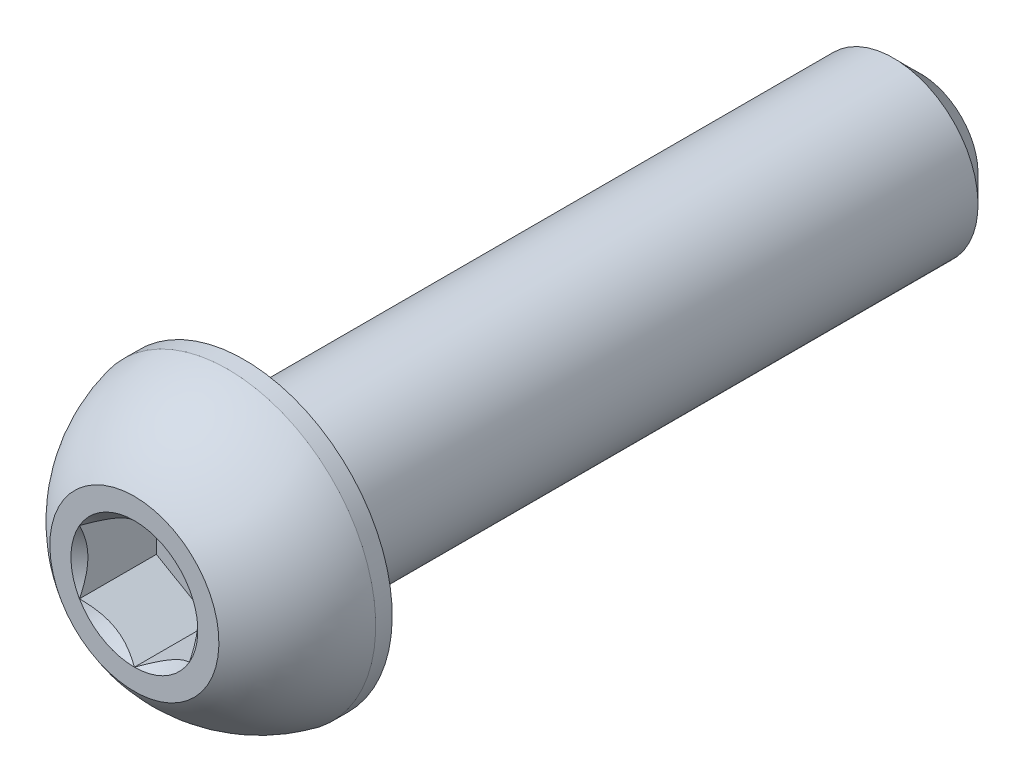
SolidWorks part; units mm, degrees
ref_plane "Front Plane" through (0, 0, 0) normal (0, 0, 1) x (1, 0, 0)
ref_plane "Top Plane" through (0, 0, 0) normal (0, 1, 0) x (1, 0, 0)
ref_plane "Right Plane" through (0, 0, 0) normal (1, 0, 0) x (0, 0, -1)
sketch "Sketch1" plane through (0, 0, 0) normal (1, 0, 0) x (0, 0, -1)
  line L0 (-4.65, 0) -> (4.65, 0) construction
  line L1 (-3.35, 1.75) -> (-3.35, -1.75) construction
  line L2 (4.65, 1) -> (4.65, -1) construction
  line L3 (4.625, 1.0433) -> (4.825, 0.6969) construction
  line L4 (4.825, 0.6969) -> (5.025, 1.0433) construction
  line L5 (5.025, 1.0433) -> (4.625, 1.0433) construction
  line L6 (4.65, 1) -> (5, 1) construction
  line L7 (4.825, 1.0433) -> (4.825, 1) construction
  line L8 (4.825, 1) -> (4.825, 0.7402) construction
  line L9 (4.825, 0.7402) -> (4.825, 0.6969) construction
  line L10 (4.8, 0.7402) -> (4.85, 0.7402)
  line L11 (4.6375, 1.0217) -> (5.0125, 1.0217)
  line L12 (4.85, 0.7402) -> (5.0125, 1.0217)
  line L13 (4.8, 0.7402) -> (4.6375, 1.0217)
  line L14 (-4.65, 0.65) -> (-4.65, -0.65) construction
  line L15 (4.65, 1) -> (-3.35, 1) construction
  point P3 (-3.35, 0)
  point P6 (-3.74, 0)
  point P21 (4.825, 1.0217)
  point P24 (-3.545, 1.75)
  point P25 (3.65, -1)
  point P26 (-4.65, 1)
  dimension "Head Height" = 1.3
  dimension "Length" = 8
  dimension "Head Dia" = 3.5
  dimension "Thread Dia" = 2
  dimension "Pitch" = 0.4
  dimension "D2" = 0.05
  dimension "Drive Size" = 1.3
  dimension "D1" = 0.91
  dimension "D3" = 0.195
  dimension "D4" = 1
sketch "Sketch2" plane through (0, 0, 0) normal (1, 0, 0) x (0, 0, -1)
  line L0 (-4.65, 0) -> (4.65, 0)
  line L1 (4.65, 0) -> (4.65, 0.68)
  line L2 (4.65, 1) -> (4.65, -1) construction
  line L3 (4.65, 0.68) -> (4.33, 1)
  line L4 (4.33, 1) -> (-3.35, 1)
  line L5 (-3.35, 1.75) -> (-3.35, -1.75) construction
  line L6 (-3.35, 1) -> (-3.35, 1.75)
  line L7 (-3.35, 1.75) -> (-3.545, 1.75)
  line L8 (4.65, 1) -> (5, 1) construction
  line L9 (-4.65, 0) -> (-4.65, 1)
  arc A0 (-4.65, 1) -> (-3.545, 1.75) centre (-3.1642, 0) cw
  dimension "D1" = 0.32
  dimension "D2" = 45
revolve "Revolve1" add sketch "Sketch2" angle 360 about L0
sketch "Sketch3" plane through (0, 0, 4.65) normal (0, 0, 1) x (1, 0, 0)
  line L1 (0, 0.7506) -> (-0.65, 0.3753)
  line L2 (-0.65, 0.3753) -> (-0.65, -0.3753)
  line L3 (-0.65, -0.3753) -> (0, -0.7506)
  line L4 (0, -0.7506) -> (0.65, -0.3753)
  line L5 (0.65, -0.3753) -> (0.65, 0.3753)
  line L6 (0.65, 0.3753) -> (0, 0.7506)
  circle A0 centre (0, 0) radius 0.65 construction
  dimension "D1" = 1.3
extrude "Cut-Extrude1" cut sketch "Sketch3" against normal up to vertex (0.91 mm away) up to point (0, 0, 3.74)
sketch "Sketch4" plane through (0, 0, 4.65) normal (0, 0, 1) x (1, 0, 0)
  circle A0 centre (0, 0) radius 0.7506
extrude "Cut-Extrude2" cut sketch "Sketch4" against normal blind 10 draft 45
split "Split1" [suppressed] bodies to split 106
sketch "Sketch5" [suppressed] plane through (0, 0, -4.65) normal (0, 0, -1) x (-1, 0, 0)
  circle A0 centre (0, 0) radius 1 construction
  circle A1 centre (0, 0) radius 1
curve "Helix/Spiral1" [suppressed] pitch 0.4 height 8.4 turns 21
sketch "Sketch6" [suppressed] plane through (0, 0, 0) normal (1, 0, 0) x (0, 0, -1)
  line L0 (4.8, 0.7402) -> (4.85, 0.7402) construction
  line L1 (4.8, 0.7402) -> (4.6375, 1.0217) construction
  line L2 (4.6375, 1.0217) -> (5.0125, 1.0217) construction
  line L3 (4.85, 0.7402) -> (5.0125, 1.0217) construction
  line L4 (4.8, 0.7402) -> (4.85, 0.7402)
  line L5 (4.8, 0.7402) -> (4.6375, 1.0217)
  line L6 (4.6375, 1.0217) -> (5.0125, 1.0217)
  line L7 (4.85, 0.7402) -> (5.0125, 1.0217)
sweep "Cut-Sweep1" [suppressed] cut profiles "Sketch6" path "Helix/Spiral1"
sketch "Sketch7" [suppressed] plane through (0, 0, 3.35) normal (0, 0, -1) x (-1, 0, 0)
  circle A1 centre (0, 0) radius 1
  circle A2 centre (0, 0) radius 1
  dimension "D1" = 0
extrude "Boss-Extrude1" [suppressed] add sketch "Sketch7" along normal blind 10 draft 30
equation "\"D2@Sketch1\" = \"Pitch@Sketch1\" / 8"
equation "\"D1@Sketch1\"=\"Drive Size@Sketch1\"*.7"
equation "\"D3@Sketch1\"=\"Head Height@Sketch1\"*.15"
equation "\"D1@Sketch2\"=\"Pitch@Sketch1\"*.8"
equation "\"D1@Sketch3\"=\"Drive Size@Sketch1\""
equation "\"D4@Helix/Spiral1\"=\"Pitch@Sketch1\""
equation "\"D3@Helix/Spiral1\"=\"Length@Sketch1\"+\"Pitch@Sketch1\""
equation "\"D4@Sketch1\"=\"Pitch@Sketch1\"*2.5"
